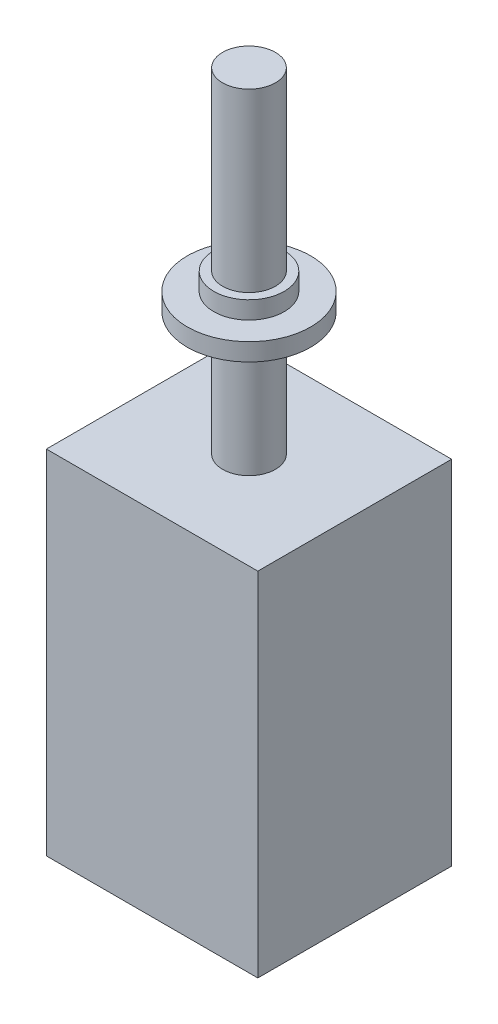
SolidWorks part; units mm, degrees
ref_plane "Front Plane" through (0, 0, 0) normal (0, 0, 1) x (1, 0, 0)
ref_plane "Top Plane" through (0, 0, 0) normal (0, 1, 0) x (1, 0, 0)
ref_plane "Right Plane" through (0, 0, 0) normal (1, 0, 0) x (0, 0, -1)
sketch "Sketch1" plane through (0, 0, 0) normal (0, 1, 0) x (1, 0, 0)
  line L1 (0, 0) -> (12, 0)
  line L2 (0, 0) -> (0, 11)
  line L3 (0, 11) -> (12, 11)
  line L4 (12, 0) -> (12, 11)
  dimension "D1" = 12
  dimension "D2" = 11
extrude "Boss-Extrude1" add sketch "Sketch1" along normal blind 20
sketch "Sketch2" plane through (0, 20, 0) normal (0, 1, 0) x (1, 0, 0)
  line L0 (-0.6033, 5.5) -> (12.6033, 5.5) construction
  line L1 (6, -0.6264) -> (6, 11.6264) construction
  line L2 (12, 11) -> (0, 11) construction
  line L3 (0, 11) -> (0, 0) construction
  circle A0 centre (6, 5.5) radius 1.5
  point P6 (6, 11)
  point P9 (0, 5.5)
  dimension "D1" = 3
extrude "Boss-Extrude2" add sketch "Sketch2" along normal blind 19
ref_plane "Plane1" through (0, 27, 0) normal (0, 1, 0) x (1, 0, 0)
sketch "Sketch3" plane through (0, 27, 0) normal (0, 1, 0) x (1, 0, 0)
  circle A0 centre (6, 5.5) radius 3.5
  dimension "D1" = 7
extrude "Boss-Extrude3" add sketch "Sketch3" along normal blind 1
sketch "Sketch4" plane through (0, 28, 0) normal (0, 1, 0) x (1, 0, 0)
  circle A0 centre (6, 5.5) radius 2
  dimension "D1" = 4
extrude "Boss-Extrude4" add sketch "Sketch4" along normal blind 1
